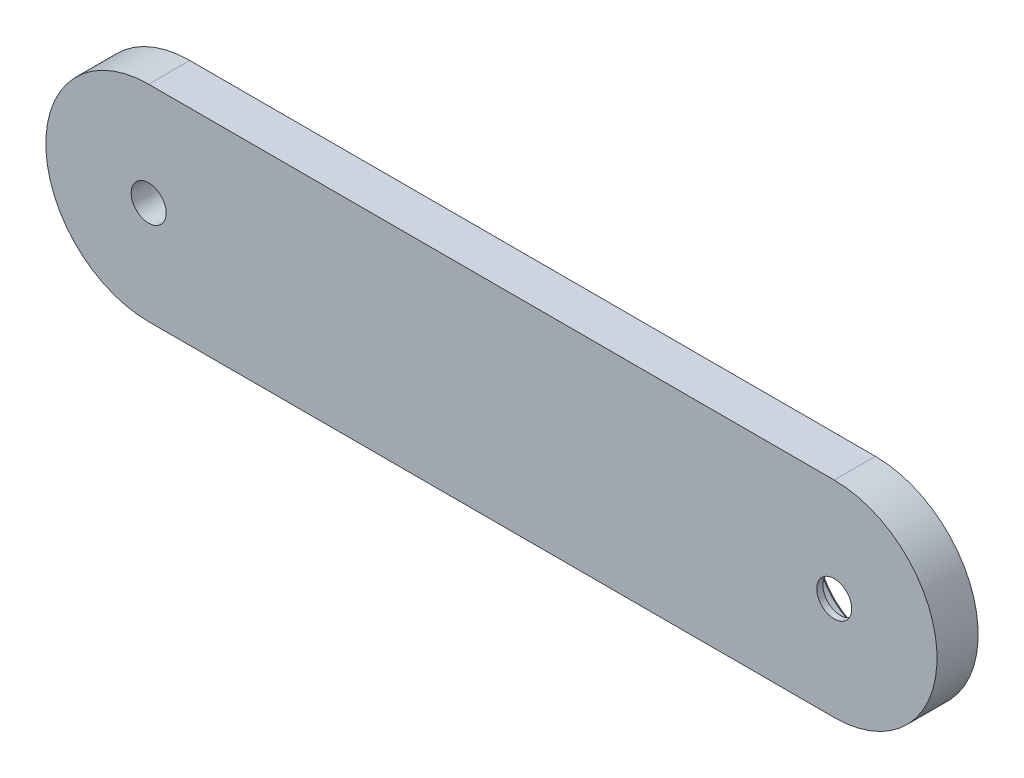
SolidWorks part; units mm, degrees
ref_plane "Front Plane" through (0, 0, 0) normal (0, 0, 1) x (1, 0, 0)
ref_plane "Top Plane" through (0, 0, 0) normal (0, 1, 0) x (1, 0, 0)
ref_plane "Right Plane" through (0, 0, 0) normal (1, 0, 0) x (0, 0, -1)
sketch "Sketch4" plane through (0, 0, 0) normal (0, 0, 1) x (1, 0, 0)
  line L0 (-50, 15) -> (50, 15)
  line L1 (50, -15) -> (-50, -15)
  line L2 (-50, 0) -> (50, 0) construction
  arc A0 (50, 15) -> (50, -15) centre (50, 0) cw
  arc A1 (-50, -15) -> (-50, 15) centre (-50, 0) cw
  dimension "D2" = 15
  dimension "D1" = 100
extrude "Boss-Extrude1" add sketch "Sketch4" along normal blind 6
sketch "Sketch9" plane through (0, 0, 0) normal (0, 0, -1) x (-1, 0, 0)
  circle A0 centre (-50, 0) radius 7.975
  dimension "D1" = 15.95
extrude "Cut-Extrude5" cut sketch "Sketch9" against normal blind 5.1
sketch "Sketch10" plane through (0, 0, 5.1) normal (0, 0, -1) x (-1, 0, 0)
  circle A0 centre (-50, 0) radius 2.55
  dimension "D1" = 5.1
extrude "Cut-Extrude6" cut sketch "Sketch10" against normal through all
sketch "Sketch11" plane through (0, 0, 0) normal (0, 0, -1) x (-1, 0, 0)
  circle A0 centre (50, 0) radius 2.55
  dimension "D1" = 5.1
extrude "Cut-Extrude7" cut sketch "Sketch11" against normal through all
chamfer "Chamfer1" distance 0.5 angle 45 1 edges at (42.025, 0, 0)
